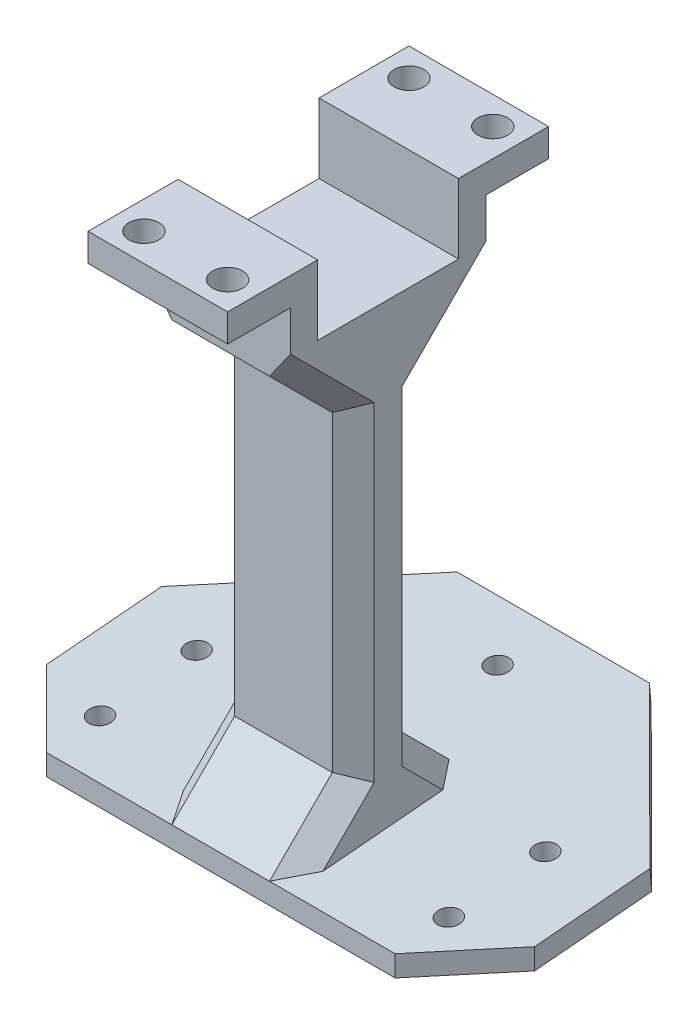
SolidWorks part; units mm, degrees
ref_plane "前视基准面" through (0, 0, 0) normal (0, 0, 1) x (1, 0, 0)
ref_plane "上视基准面" through (0, 0, 0) normal (0, 1, 0) x (1, 0, 0)
ref_plane "右视基准面" through (0, 0, 0) normal (1, 0, 0) x (0, 0, -1)
sketch "Sketch1" plane through (0, 0, 0) normal (0, 0, 1) x (1, 0, 0)
  line L0 (-416.3994, 251.675) -> (-416.3994, 294.0309) construction
  line L3 (-426.3994, 294.3348) -> (-406.3994, 294.3348)
  line L4 (-426.3994, 294.3348) -> (-426.3994, 240.9903)
  line L5 (-426.3994, 240.9903) -> (-406.3994, 240.9903)
  line L6 (-406.3994, 294.3348) -> (-406.3994, 240.9903)
  dimension "D1" = 10
  dimension "D2" = 10
extrude "Boss-Extrude1" add sketch "Sketch1" against normal blind 28
ref_plane "Plane1" through (0, 222.9297, 19.5038) normal (0, 0.9962, 0.0872) x (1, 0, 0)
sketch "Sketch2" plane through (0, 240.9903, 0) normal (0, -1, 0) x (1, 0, 0)
  line L4 (-406.3994, 0) -> (-426.3994, 0)
  line L5 (-426.3994, 0) -> (-426.3994, -28)
  line L6 (-426.3994, -28) -> (-406.3994, -28)
  line L7 (-406.3994, -28) -> (-406.3994, 0)
  line L8 (-406.3994, 0) -> (-426.3994, 0)
  line L9 (-426.3994, 0) -> (-426.3994, -28)
  line L10 (-426.3994, -28) -> (-406.3994, -28)
  line L11 (-406.3994, -28) -> (-406.3994, 0)
  dimension "D1" = 0
extrude "Boss-Extrude2" add sketch "Sketch2" along normal up to surface (16.3542 mm away) up to plane "Plane1"
sketch "Sketch3" plane through (-426.3994, 0, 0) normal (-1, 0, 0) x (0, 0, 1)
  line L36 (-28, 300.3348) -> (-37, 300.3348)
  line L37 (-37, 300.3348) -> (-37, 304.3348)
  line L38 (-37, 304.3348) -> (-24.1, 304.3348)
  line L46 (9, 300.3348) -> (9, 304.3348)
  line L47 (0, 300.3348) -> (9, 300.3348)
  line L48 (0, 300.3348) -> (0, 294.3348)
  line L49 (-3.9, 304.3348) -> (-3.9, 294.3348)
  line L50 (9, 304.3348) -> (-3.9, 304.3348)
  line L51 (-24.1, 304.3348) -> (-24.1, 294.3348)
  line L52 (-28, 294.3348) -> (-28, 300.3348)
  line L53 (-28, 294.3348) -> (-24.1, 294.3348)
  line L54 (-3.9, 294.3348) -> (0, 294.3348)
extrude "Boss-Extrude3" add sketch "Sketch3" against normal up to vertex (20 mm away) up to point (-406.3994, 294.3348, 0)
sketch "Sketch4" plane through (0, 304.3348, 0) normal (0, 1, 0) x (1, 0, 0)
  line L0 (-426.3994, 14) -> (-406.3994, 14) construction
  line L1 (-426.3994, 24.1) -> (-426.3994, 3.9) construction
  line L2 (-406.3994, 24.1) -> (-406.3994, 3.9) construction
  line L6 (-406.3994, 37) -> (-426.3994, 37) construction
  line L7 (-426.3994, 24.1) -> (-426.3994, 37) construction
  line L8 (-406.3994, 24.1) -> (-406.3994, 37) construction
  circle A0 centre (-422.3994, 33) radius 2.15
  circle A1 centre (-410.3994, 33) radius 2.15
  circle A2 centre (-410.3994, -5) radius 2.15
  circle A3 centre (-422.3994, -5) radius 2.15
  dimension "D1" = 4.3
  dimension "D2" = 4
  dimension "D3" = 4
  dimension "D4" = 4
  dimension "D5" = 4
extrude "Cut-Extrude1" cut sketch "Sketch4" against normal blind 10
sketch "Sketch6" plane through (0, 222.9297, 19.5038) normal (0, -0.9962, -0.0872) x (1, 0, 0)
  line L10 (-451.3994, -19.5783) -> (-451.3994, -46.4721)
  line L11 (-451.3994, -46.4721) -> (-430.1862, -67.6853)
  line L12 (-430.1862, -67.6853) -> (-402.6126, -67.6853)
  line L13 (-416.3994, -19.5783) -> (-416.3994, -89.5198) construction
  line L14 (-426.3994, -19.5783) -> (-406.3994, -19.5783) construction
  line L15 (-451.3994, -19.5783) -> (-381.3994, -19.5783)
  line L16 (-426.3994, -47.6853) -> (-426.3994, -19.5783) construction
  line L17 (-406.3994, -47.6853) -> (-426.3994, -47.6853) construction
  line L18 (-381.3994, -46.4721) -> (-402.6126, -67.6853)
  line L19 (-381.3994, -19.5783) -> (-381.3994, -46.4721)
  circle A5 centre (-441.3994, -27.5783) radius 1.6
  circle A6 centre (-441.3994, -41.4721) radius 1.6
  circle A7 centre (-391.3994, -41.4721) radius 1.6
  circle A8 centre (-391.3994, -27.5783) radius 1.6
  circle A9 centre (-391.3994, -41.4721) radius 1.6
  circle A10 centre (-391.3994, -27.5783) radius 1.6
  circle A11 centre (-416.3994, -59.6853) radius 1.6
  point P24 (-416.3994, -67.6853)
  line M11 (-406.3994, -47.6853) -> (-406.3994, -19.5783)
  line M13 (-426.3994, -19.5783) -> (-426.3994, -47.6853)
  line M14 (-426.3994, -47.6853) -> (-406.3994, -47.6853)
  dimension "D6" = 10
  dimension "D7" = 5
  dimension "D8" = 8
  dimension "D9" = 3.2
  dimension "D10" = 8
  dimension "D5" = 10
  dimension "D1" = 25
  dimension "D2" = 20
  dimension "D3" = 45
  dimension "D4" = 30
extrude "Boss-Extrude5" add sketch "Sketch6" against normal blind 3 contours L13 L15 L10 L11 L12 A11 A6 A5 M14 M13 | L13 A11 L12 L18 L19 L15 A8 A7 M14 M11 region at (-434.8617, 226.6626, -23.163) region at (-397.9372, 226.6626, -23.163)
sketch "Sketch7" plane through (0, 0, 0) normal (0, 0, 1) x (1, 0, 0)
  line L1 (-363.4408, 231.1515) -> (-467.8148, 231.1515)
  line L2 (-363.4408, 231.1515) -> (-363.4408, 214.507)
  line L3 (-363.4408, 214.507) -> (-467.8148, 214.507)
  line L4 (-467.8148, 231.1515) -> (-467.8148, 214.507)
extrude "Cut-Extrude2" cut sketch "Sketch7" along normal blind 3
chamfer "Chamfer1" distance 10 angle 45 2 edges at (-381.3994, 226.1418, 0) (-451.3994, 226.1418, 0)
sketch "Sketch8" plane through (-426.3994, 0, 0) normal (-1, 0, 0) x (0, 0, 1)
  line L0 (-28, 290.3348) -> (-19, 281.3348)
  line L1 (-28, 300.3348) -> (-28, 230.0972) construction
  line L2 (-19, 281.3348) -> (-19, 236.6475)
  line L3 (-19, 236.6475) -> (-25.7474, 229.9001)
  line L4 (-28, 230.0972) -> (-28, 290.3348)
  line L5 (0, 290.3348) -> (-9, 281.3348)
  line L6 (0, 300.3348) -> (0, 227.6475) construction
  line L7 (-9, 281.3348) -> (-9, 236.6475)
  line L8 (-9, 236.6475) -> (0, 227.6475)
  line L9 (0, 227.6475) -> (0, 290.3348)
  line L10 (-28, 230.0972) -> (-28, 300.3348) construction
  line L12 (-24.1, 294.3348) -> (-3.9, 294.3348) construction
  line L13 (-28, 230.0972) -> (-25.7474, 229.9001)
  line L14 (-10, 228.5224) -> (-26.5299, 229.9686) construction
  dimension "D1" = 45
  dimension "D2" = 45
  dimension "D3" = 10
  dimension "D4" = 4
  dimension "D5" = 4
extrude "Cut-Extrude3" cut sketch "Sketch8" against normal blind 60
chamfer "Chamfer2" distance 3 12 edges at (-426.3994, 232.1475, -4.5) (-426.3994, 258.9912, -9) (-426.3994, 285.8348, -4.5) (-406.3994, 232.1475, -4.5) (-406.3994, 285.8348, -4.5) (-406.3994, 258.9912, -9) (-426.3994, 233.2738, -22.3737) (-426.3994, 285.8348, -23.5) (-426.3994, 258.9912, -19) (-406.3994, 233.2738, -22.3737) (-406.3994, 258.9912, -19) (-406.3994, 285.8348, -23.5)
